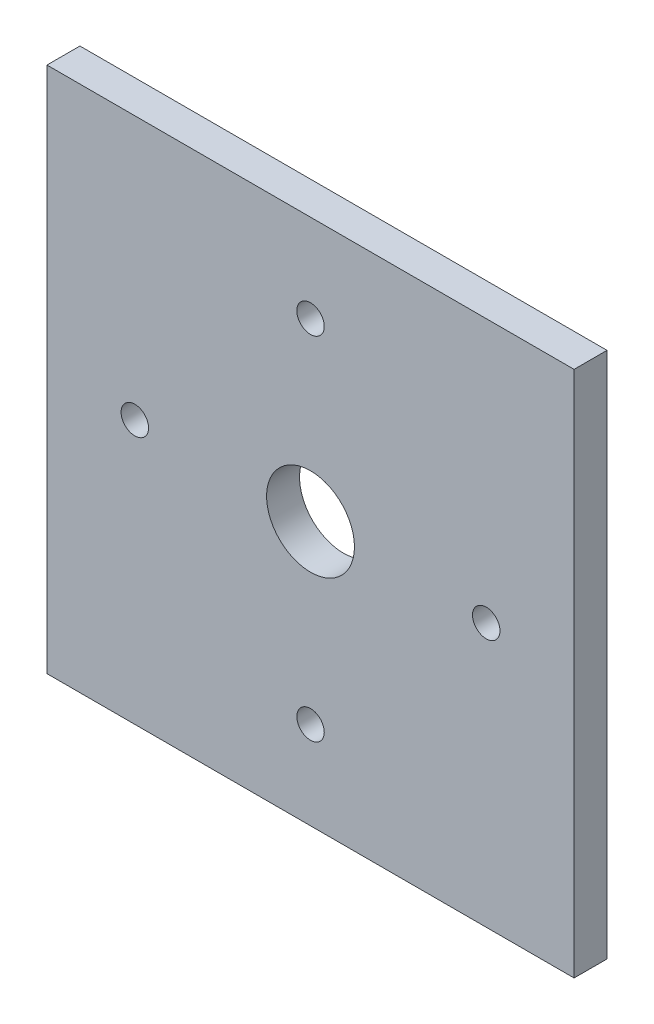
SolidWorks part; units mm, degrees
ref_plane "Front Plane" through (0, 0, 0) normal (0, 0, 1) x (1, 0, 0)
ref_plane "Top Plane" through (0, 0, 0) normal (0, 1, 0) x (1, 0, 0)
ref_plane "Right Plane" through (0, 0, 0) normal (1, 0, 0) x (0, 0, -1)
sketch "Sketch1" plane through (0, 0, 0) normal (0, 0, 1) x (1, 0, 0)
  line L1 (0, 0) -> (152.4, 0)
  line L2 (0, 0) -> (0, 152.4)
  line L3 (0, 152.4) -> (152.4, 152.4)
  line L4 (152.4, 0) -> (152.4, 152.4)
extrude "plate" add sketch "Sketch1" along normal blind 9.525
sketch "Sketch2" plane through (0, 0, 0) normal (0, 0, 1) x (1, 0, 0)
  circle A0 centre (25.4, 25.4) radius 3.175
sketch "Sketch3" plane through (0, 0, 0) normal (0, 0, 1) x (1, 0, 0)
  circle A0 centre (127, 76.2) radius 3.9687
  circle A1 centre (76.2, 127) radius 3.9687
  circle A2 centre (25.4, 76.2) radius 3.9688
  circle A3 centre (76.2, 25.4) radius 3.9687
extrude "bolt_one_sketch" cut sketch "Sketch3" along normal through all
sketch "Sketch4" plane through (0, 0, 0) normal (0, 0, 1) x (1, 0, 0)
  circle A0 centre (76.2, 76.2) radius 12.7
extrude "centre_bore2" cut sketch "Sketch4" along normal through all
sketch "Sketch5" plane through (0, 0, 0) normal (0, 0, 1) x (1, 0, 0)
  circle A0 centre (127, 76.2) radius 3.9687
ref_axis "Axis1" through (76.2, 76.2, 9.525) along (0, 0, -1)
